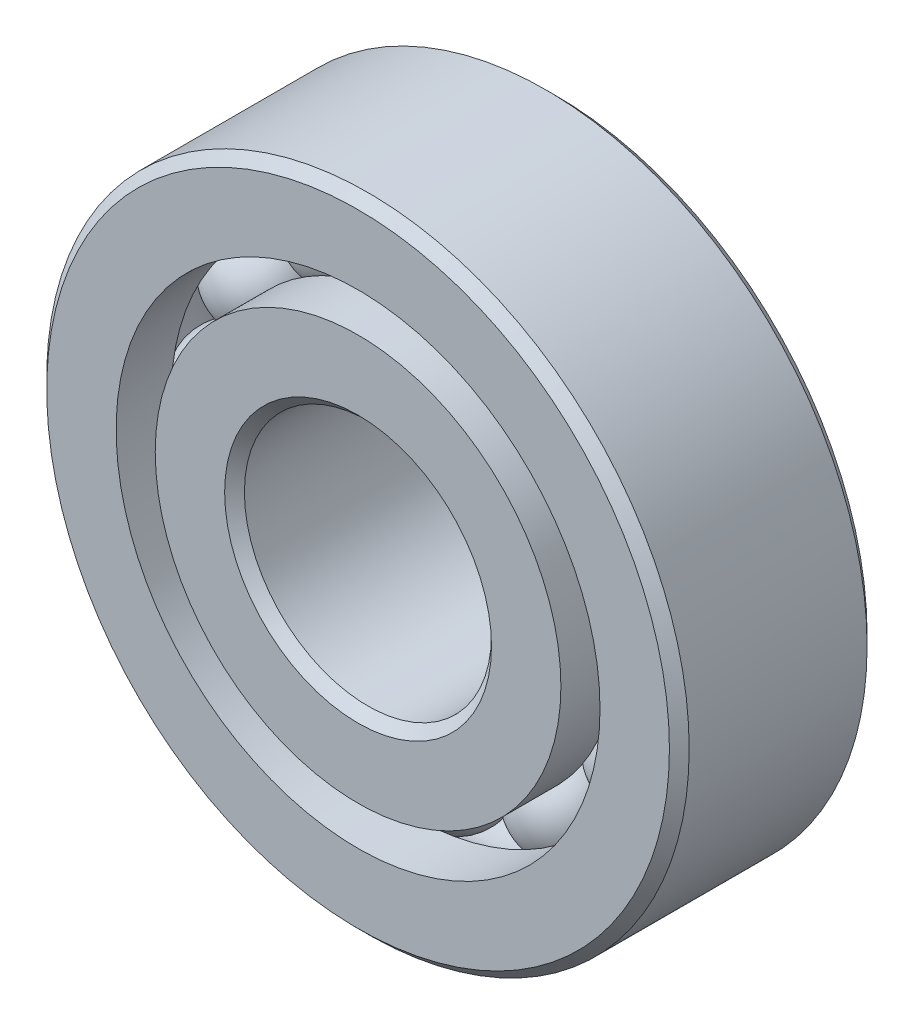
SolidWorks part; units mm, degrees
ref_plane "Front Plane" through (0, 0, 0) normal (0, 0, 1) x (1, 0, 0)
ref_plane "Top Plane" through (0, 0, 0) normal (0, 1, 0) x (1, 0, 0)
ref_plane "Right Plane" through (0, 0, 0) normal (1, 0, 0) x (0, 0, -1)
sketch "Sketch1" plane through (0, 0, 0) normal (1, 0, 0) x (0, 0, -1)
  line L0 (-4, 0) -> (4, 0) construction
  line L1 (0, 13) -> (0, -13) construction
  line L2 (3.6, 13) -> (-3.6, 13)
  line L3 (-3.6, 13) -> (-4, 12.6)
  line L4 (-4, 12.6) -> (-4, 9.7912)
  line L5 (-4, 9.7912) -> (-1.7778, 9.7912)
  line L6 (4, 9.7912) -> (1.7778, 9.7912)
  line L7 (4, 12.6) -> (4, 9.7912)
  line L8 (3.6, 13) -> (4, 12.6)
  line L9 (0, 13) -> (0, 9) construction
  line L10 (0, 9) -> (0, 5) construction
  arc A0 (-1.7778, 9.7912) -> (1.7778, 9.7912) centre (0, 9) cw
  point P14 (0, 5)
  dimension "Width" = 8
  dimension "OD" = 26
  dimension "D1" = 45
  dimension "D2" = 0.4
  dimension "Shaft Dia" = 10
  dimension "D3" = 3.5556
  dimension "D4" = 0.7912
revolve "Revolve1" add sketch "Sketch1" angle 360 about L0
sketch "Sketch3" plane through (0, 0, 0) normal (1, 0, 0) x (0, 0, -1)
  line L0 (-4, 8.2088) -> (-1.7778, 8.2088)
  line L1 (0, 13) -> (0, -13) construction
  line L2 (-4, 12.6) -> (-4, 9.7912) construction
  line L3 (-4, 8.2088) -> (-4, 5.4)
  line L4 (-3.6, 13) -> (-4, 12.6) construction
  line L5 (-4, 5.4) -> (-3.6, 5)
  line L6 (-3.6, 5) -> (3.6, 5)
  line L7 (3.6, 13) -> (3.6, -13) construction
  line L8 (3.6, 5) -> (4, 5.4)
  line L9 (4, -12.6) -> (4, 12.6) construction
  line L10 (4, 5.4) -> (4, 8.2088)
  line L11 (4, 8.2088) -> (1.7778, 8.2088)
  line L13 (3.6, 13) -> (4, 12.6) construction
  arc A0 (1.7778, 9.7912) -> (-1.7778, 9.7912) centre (0, 9) ccw construction
  arc A1 (1.7778, 8.2088) -> (-1.7778, 8.2088) centre (0, 9) cw
revolve "Revolve3" add sketch "Sketch3" angle 360 about L0
sketch "Sketch4" plane through (0, 0, 0) normal (1, 0, 0) x (0, 0, -1)
  line L0 (-1.9459, 9) -> (1.9459, 9)
  arc A2 (-1.9459, 9) -> (1.9459, 9) centre (0, 9) cw
  arc A3 (1.7778, 9.7912) -> (-1.7778, 9.7912) centre (0, 9) ccw construction
revolve "Revolve4" add sketch "Sketch4" angle 360 about L0
ref_axis "Axis1" through (0, 0, -4) along (0, 0, 1)
pattern_circular "CirPattern1" count 12 every 30 about axis through (0, 0, -4) along (0, 0, 1) of bodies 104
sketch "Sketch5" plane through (0, 0, 0) normal (1, 0, 0) x (0, 0, -1)
  line L0 (-4, 9.7912) -> (-1.7778, 9.7912) construction
  line L1 (-3.8, 9.7912) -> (-1.9459, 9.7912)
  line L2 (-3.8, 9.7912) -> (-3.8, 8.2088)
  line L3 (-3.8, 8.2088) -> (-1.9459, 8.2088)
  line L4 (-1.9459, 9.7912) -> (-1.9459, 8.2088)
  line L5 (-4, 8.2088) -> (-1.7778, 8.2088) construction
  line L6 (4, 9.7912) -> (1.7778, 9.7912) construction
  line L7 (3.8, 9.7912) -> (1.9459, 9.7912)
  line L8 (3.8, 9.7912) -> (3.8, 8.2088)
  line L9 (3.8, 8.2088) -> (1.9459, 8.2088)
  line L10 (1.9459, 9.7912) -> (1.9459, 8.2088)
  line L11 (4, 8.2088) -> (1.7778, 8.2088) construction
  line L12 (-3.6, 13) -> (-4, 12.6) construction
  point P18 (-3.8, 12.8)
equation "\"D2@Sketch1\" = \"Width@Sketch1\"*.05"
equation "\"D3@Sketch1\" = \"Width@Sketch1\"/2.25"
equation "\"D4@Sketch1\" = (((\"OD@Sketch1\"-\"Width@Sketch1\")/2)/3.25)/3.5"
equation "\"D2@CirPattern1\" = 360/\"Balls@CirPattern1\""
